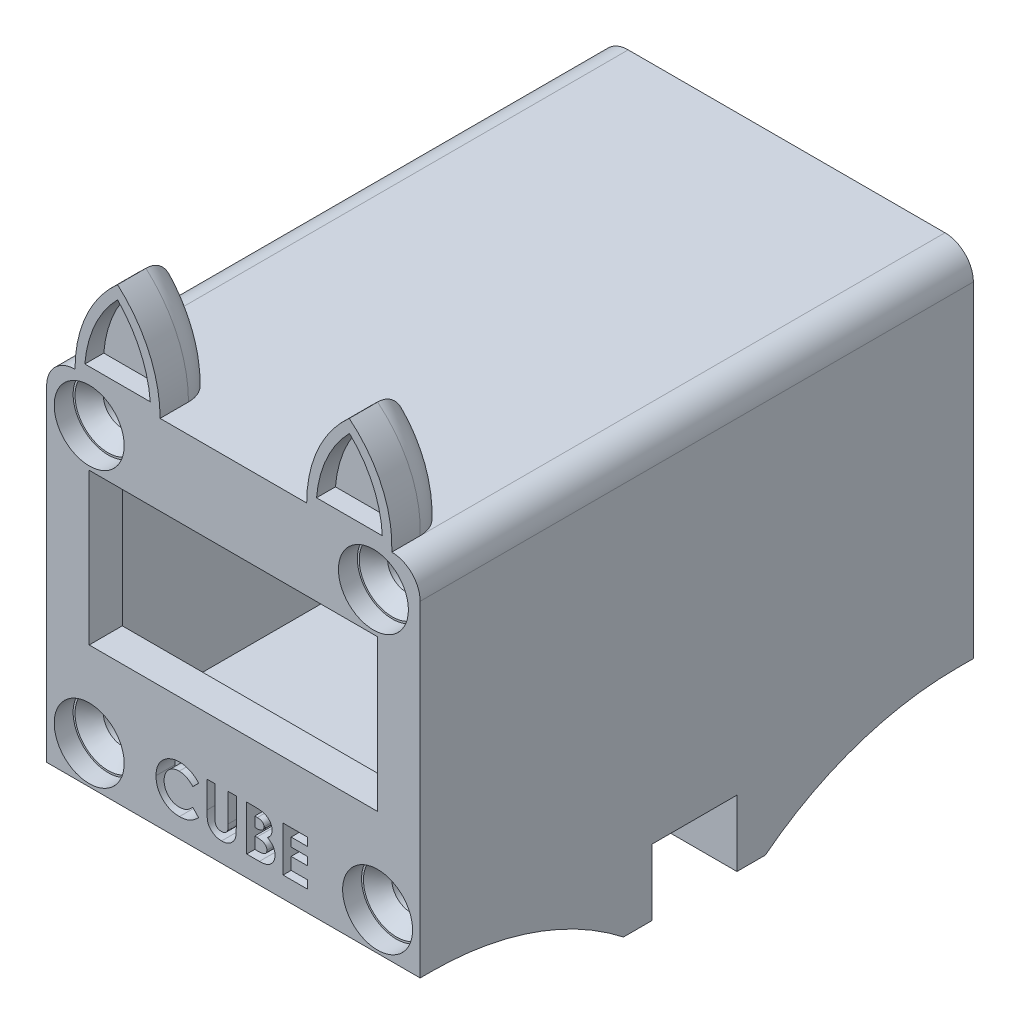
SolidWorks part; units mm, degrees
ref_plane "Plan de face" through (0, 0, 0) normal (0, 0, 1) x (1, 0, 0)
ref_plane "Plan de dessus" through (0, 0, 0) normal (0, 1, 0) x (1, 0, 0)
ref_plane "Plan de droite" through (0, 0, 0) normal (1, 0, 0) x (0, 0, -1)
sketch "Esquisse1" plane through (0, 0, 0) normal (0, 0, 1) x (1, 0, 0)
  line L0 (-17.8827, 11.8632) -> (15.6173, 11.8632)
  line L1 (-20.8827, 8.8632) -> (-20.8827, -25.6368)
  line L2 (18.6173, 8.8632) -> (18.6173, -25.6368)
  line L3 (-20.8827, -25.6368) -> (18.6173, -25.6368)
  line L5 (-16.3827, 3.3632) -> (14.1173, 3.3632)
  line L6 (-16.3827, 3.3632) -> (-16.3827, -12.6368)
  line L7 (-16.3827, -12.6368) -> (14.1173, -12.6368)
  line L8 (14.1173, 3.3632) -> (14.1173, -12.6368)
  arc A0 (18.6173, 8.8632) -> (15.6173, 11.8632) centre (15.6173, 8.8632) ccw
  arc A1 (-20.8827, 8.8632) -> (-17.8827, 11.8632) centre (-17.8827, 8.8632) cw
  point P6 (18.6173, 11.8632)
  point P9 (-20.8827, 11.8632)
  dimension "D3" = 3
  dimension "D1" = 39.5
  dimension "D2" = 37.5
  dimension "D4" = 8.5
  dimension "D5" = 4.5
  dimension "D6" = 16
  dimension "D7" = 4.5
extrude "Boss.-Extru.1" add sketch "Esquisse1" along normal blind 3.5
sketch "Esquisse2" plane through (0, 0, 0) normal (0, 0, -1) x (-1, 0, 0)
  line L8 (-17.1173, 8.8632) -> (-17.1173, -24.1368)
  line L9 (-17.1173, -24.1368) -> (19.3827, -24.1368)
  line L10 (19.3827, -24.1368) -> (19.3827, 8.8632)
  line L11 (17.8827, 10.3632) -> (-15.6173, 10.3632)
  line L12 (-17.1173, 8.8632) -> (-17.1173, -24.1368)
  line L13 (-17.1173, -24.1368) -> (19.3827, -24.1368)
  line L14 (19.3827, -24.1368) -> (19.3827, 8.8632)
  line L15 (17.8827, 10.3632) -> (-15.6173, 10.3632)
  line L20 (-18.6173, 8.8632) -> (-18.6173, -25.6368)
  line L21 (-18.6173, -25.6368) -> (20.8827, -25.6368)
  line L22 (20.8827, -25.6368) -> (20.8827, 8.8632)
  line L23 (17.8827, 11.8632) -> (-15.6173, 11.8632)
  line L24 (-18.6173, 8.8632) -> (-18.6173, -25.6368)
  line L25 (-18.6173, -25.6368) -> (20.8827, -25.6368)
  line L26 (20.8827, -25.6368) -> (20.8827, 8.8632)
  line L27 (17.8827, 11.8632) -> (-15.6173, 11.8632)
  arc A4 (-15.6173, 10.3632) -> (-17.1173, 8.8632) centre (-15.6173, 8.8632) ccw
  arc A5 (19.3827, 8.8632) -> (17.8827, 10.3632) centre (17.8827, 8.8632) ccw
  arc A6 (-15.6173, 10.3632) -> (-17.1173, 8.8632) centre (-15.6173, 8.8632) ccw
  arc A7 (19.3827, 8.8632) -> (17.8827, 10.3632) centre (17.8827, 8.8632) ccw
  arc A10 (-15.6173, 11.8632) -> (-18.6173, 8.8632) centre (-15.6173, 8.8632) ccw
  arc A11 (20.8827, 8.8632) -> (17.8827, 11.8632) centre (17.8827, 8.8632) ccw
  arc A12 (-15.6173, 11.8632) -> (-18.6173, 8.8632) centre (-15.6173, 8.8632) ccw
  arc A13 (20.8827, 8.8632) -> (17.8827, 11.8632) centre (17.8827, 8.8632) ccw
  dimension "D1" = 1.5
  dimension "D2" = 0
extrude "Boss.-Extru.2" add sketch "Esquisse2" along normal blind 55
sketch "Esquisse3" plane through (0, 0, 0) normal (0, 0, -1) x (-1, 0, 0)
  line L0 (-17.1173, -24.1368) -> (19.3827, -24.1368) construction
  line L1 (-17.1173, -24.1368) -> (19.3827, -24.1368)
  line L2 (-17.1173, -24.1368) -> (-17.1173, -19.1368)
  line L3 (-17.1173, -19.1368) -> (19.3827, -19.1368)
  line L4 (19.3827, -24.1368) -> (19.3827, -19.1368)
  line L5 (-17.1173, -24.1368) -> (19.3827, -24.1368) construction
  line L6 (19.3827, -24.1368) -> (19.3827, 8.8632) construction
  line L7 (17.8827, 10.3632) -> (-15.6173, 10.3632) construction
  line L8 (-17.1173, 10.3632) -> (19.3827, 10.3632)
  line L9 (-17.1173, 10.3632) -> (-17.1173, 5.3632)
  line L10 (-17.1173, 5.3632) -> (19.3827, 5.3632)
  line L11 (19.3827, 10.3632) -> (19.3827, 5.3632)
  line L12 (-17.1173, 8.8632) -> (-17.1173, -24.1368) construction
  line L13 (-5.1173, -19.1368) -> (7.3827, -19.1368)
  line L14 (-5.1173, -19.1368) -> (-5.1173, -21.6368)
  line L15 (-5.1173, -21.6368) -> (7.3827, -21.6368)
  line L16 (7.3827, -19.1368) -> (7.3827, -21.6368)
  line L17 (-5.1173, 10.3632) -> (7.3827, 10.3632)
  line L18 (-5.1173, 10.3632) -> (-5.1173, 5.3632)
  line L19 (-5.1173, 5.3632) -> (7.3827, 5.3632)
  line L20 (7.3827, 10.3632) -> (7.3827, 5.3632)
  line M10 (17.8827, 10.3632) -> (-15.6173, 10.3632)
  arc M11 (-15.6173, 10.3632) -> (-17.1173, 8.8632) centre (-15.6173, 8.8632) ccw
  line M12 (-17.1173, 8.8632) -> (-17.1173, -24.1368)
  line M13 (-17.1173, -24.1368) -> (19.3827, -24.1368)
  line M14 (19.3827, -24.1368) -> (19.3827, 8.8632)
  arc M15 (19.3827, 8.8632) -> (17.8827, 10.3632) centre (17.8827, 8.8632) ccw
  dimension "D1" = 5
  dimension "D2" = 0
  dimension "D3" = 5
  dimension "D4" = 2.5
  dimension "D5" = 12
  dimension "D6" = 12
  dimension "D7" = 12
  dimension "D8" = 12
  dimension "D9" = 0
  dimension "D10" = 0
extrude "Boss.-Extru.3" add sketch "Esquisse3" along normal blind 1.5 contours L18 L10 M10 M11 M12 | L20 L10 M10 M14 M15 | L3 L16 L15 L14 M12 M13 M14 region at (-1.1327, -21.8951, 0) region at (11.0713, 7.8456, 0) region at (-13.3367, 7.8456, 0)
fillet "Congé1" radius 2.5 1 edges at (-1.1327, -21.6368, -1.5)
sketch "Esquisse8" plane through (0, 0, 0) normal (0, 0, -1) x (-1, 0, 0)
  line L0 (7.3827, 10.3632) -> (7.3827, 5.3632) construction
  line L1 (-5.1173, 5.3632) -> (7.3827, 5.3632)
  line L2 (-5.1173, 5.3632) -> (-5.1173, 10.3632)
  line L3 (-5.1173, 10.3632) -> (7.3827, 10.3632)
  line L4 (7.3827, 5.3632) -> (7.3827, 10.3632)
  line L5 (7.3827, 10.3632) -> (7.3827, 5.3632) construction
extrude "Enlèv. mat.-Extru.6" cut sketch "Esquisse8" against normal blind 2
sketch "Esquisse4" plane through (0, 0, 3.5) normal (0, 0, 1) x (1, 0, 0)
  line L0 (-20.8827, 7.4632) -> (18.6173, 7.4632) construction
  line L1 (-20.8827, 8.8632) -> (-20.8827, -25.6368) construction
  line L2 (18.6173, -25.6368) -> (18.6173, 8.8632) construction
  line L4 (-20.8827, -25.6368) -> (18.6173, -25.6368) construction
  line L5 (14.1173, -25.6368) -> (14.1173, 11.8632) construction
  line L6 (15.6173, 11.8632) -> (-17.8827, 11.8632) construction
  line L8 (-16.3827, -25.6368) -> (-16.3827, 11.8632) construction
  line L10 (-20.8827, -21.6368) -> (18.6173, -21.6368) construction
  circle A0 centre (-16.3827, 7.4632) radius 2
  circle A1 centre (13.6721, 7.4632) radius 2
  circle A2 centre (14.1173, -21.6368) radius 2
  circle A3 centre (-16.3827, -21.6368) radius 2
  point P6 (-16.3827, 7.4632)
  point P17 (13.6721, 7.4632)
  point P18 (14.1173, -21.6368)
  point P19 (-16.3827, -21.6368)
  dimension "D5" = 4
  dimension "D6" = 4
  dimension "D7" = 4
  dimension "D8" = 4
  dimension "D1" = 4
  dimension "D2" = 4.5
  dimension "D3" = 4.4
  dimension "D4" = 4.5
extrude "Enlèv. mat.-Extru.1" cut sketch "Esquisse4" against normal blind 9.5
sketch "Esquisse5" plane through (0, 0, 3.5) normal (0, 0, 1) x (1, 0, 0)
  line L0 (-15.5568, -23.4583) -> (13.2914, -23.4583) construction
  line L1 (-20.8827, -25.6368) -> (18.6173, -25.6368) construction
  circle A0 centre (-16.3827, -21.6368) radius 3.7
  circle A1 centre (13.6721, 7.4632) radius 3.7
  circle A2 centre (-16.3827, 7.4632) radius 3.7
  circle A3 centre (14.1173, -21.6368) radius 3.7
  circle A4 centre (-16.3827, -21.6368) radius 2 construction
  circle A5 centre (14.1173, -21.6368) radius 2 construction
  text T0 "<b>CUBE</b>" font "Century Gothic" height in points 18
  dimension "D1" = 7.4
  dimension "D2" = 7.4
  dimension "D3" = 7.4
  dimension "D4" = 7.4
  dimension "D5" = 180
extrude "Enlèv. mat.-Extru.5" cut sketch "Esquisse5" against normal blind 2
chamfer "Chanfrein1" distance 1.5 angle 45 4 edges at (-14.3827, -21.6368, 1.5) (-14.3827, 7.4632, 1.5) (15.6721, 7.4632, 1.5) (16.1173, -21.6368, 1.5)
sketch "Esquisse6" plane through (0, 0, -55) normal (0, 0, -1) x (-1, 0, 0)
  line L0 (1.1327, 10.3632) -> (1.1327, -24.1368) construction
  line L1 (7.3827, 10.3632) -> (-5.1173, 10.3632) construction
  line L2 (-17.1173, -24.1368) -> (19.3827, -24.1368) construction
  line L3 (-2.6173, 8.1132) -> (-2.6173, 10.3632)
  line L4 (17.8827, 10.3632) -> (-15.6173, 10.3632) construction
  line L5 (-2.6173, 10.3632) -> (-2.6173, 11.8632)
  line L6 (4.8827, 8.1132) -> (4.8827, 10.3632)
  line L7 (1.1327, -6.8868) -> (9.6914, -6.8868) construction
  line L8 (4.8827, -21.8868) -> (4.8827, -24.1368)
  line L9 (-2.6173, -24.1368) -> (4.8827, -24.1368)
  line L10 (-2.6173, -21.8868) -> (-2.6173, -24.1368)
  line L11 (17.8827, 11.8632) -> (-15.6173, 11.8632) construction
  line L12 (-2.6173, 11.8632) -> (4.8827, 11.8632)
  line L13 (4.8827, 11.8632) -> (4.8827, 10.3632)
  line L14 (4.8827, -24.1368) -> (4.8827, -25.6368)
  line L15 (-18.6173, -25.6368) -> (20.8827, -25.6368) construction
  line L16 (4.8827, -25.6368) -> (-2.6173, -25.6368)
  line L17 (-2.6173, -25.6368) -> (-2.6173, -24.1368)
  circle A0 centre (1.1327, 8.1132) radius 2.25
  circle A1 centre (1.1327, 8.1132) radius 3.75
  circle A2 centre (1.1327, -21.8868) radius 3.75
  circle A3 centre (1.1327, -21.8868) radius 2.25
  point P31 (1.1327, 11.8632)
  line M6 (-18.6173, -25.6368) -> (20.8827, -25.6368)
  line M9 (17.8827, 11.8632) -> (-15.6173, 11.8632)
  line M12 (-15.6173, 10.3632) -> (17.8827, 10.3632)
  line M15 (19.3827, -24.1368) -> (-17.1173, -24.1368)
  dimension "D1" = 4.5
  dimension "D2" = 3.75
extrude "Boss.-Extru.5" add sketch "Esquisse6" against normal blind 7 contours A2 L10 M15 | A2 L17 M6 M15 | A2 L16 L14 M15 | A2 L9 M15 | L8 A2 M15 | A3 L9 A2 M15 | A1 A0 M12 | A1 L12 L5 M12 | A1 L3 M12 | A1 M12 | A1 L13 M12 M9 | A1 L6 M12 region at (2.3337, 9.2686, -55) region at (2.3968, 9.8125, -55) region at (1.6458, 11.2886, -55) region at (-4.6622, 9.8125, -55) region at (-1.1327, 10.9748, -55) region at (-3.9112, 11.2886, -55) region at (-4.5991, -23.0423, -55) region at (-4.6622, -23.5862, -55) region at (-3.9112, -25.0623, -55) region at (2.3968, -23.5862, -55) region at (-1.1327, -24.7485, -55) region at (1.6458, -25.0623, -55)
sketch "Esquisse7" plane through (0, 0, -55) normal (0, 0, -1) x (-1, 0, 0)
  line L0 (7.3827, 10.3632) -> (-5.1173, 10.3632) construction
  line L1 (-3.1173, 10.3632) -> (5.3827, 10.3632)
  line L2 (-3.1173, 10.3632) -> (-3.1173, 8.1132)
  line L3 (-3.1173, 8.1132) -> (5.3827, 8.1132)
  line L4 (5.3827, 10.3632) -> (5.3827, 8.1132)
  line L5 (-2.6173, 8.1132) -> (-2.6173, 10.3632) construction
  line L6 (4.8827, 8.1132) -> (4.8827, 10.3632) construction
  arc A0 (-3.1173, 8.1132) -> (5.3827, 8.1132) centre (1.1327, 8.1132) ccw
  arc A1 (4.8827, 8.1132) -> (-2.6173, 8.1132) centre (1.1327, 8.1132) cw
  line M13 (4.8827, 8.1132) -> (4.8827, 10.3632)
  line M14 (4.8827, 10.3632) -> (17.8827, 10.3632)
  line M24 (-15.6173, 10.3632) -> (-2.6173, 10.3632)
  line M25 (-2.6173, 10.3632) -> (-2.6173, 8.1132)
  arc M26 (-2.6173, 8.1132) -> (4.8827, 8.1132) centre (1.1327, 8.1132) ccw
  dimension "D1" = 2.25
  dimension "D2" = 0.5
  dimension "D3" = 0.5
extrude "Boss.-Extru.6" add sketch "Esquisse7" against normal blind 7 contours L3 A0 M26 | L4 L3 M14 M13 | L2 L3 M25 M24 region at (2.8673, 9.2382, -55) region at (2.8673, 8.0181, -55) region at (-5.1327, 9.2382, -55)
sketch "Esquisse10" plane through (0, 0, 3.5) normal (0, 0, 1) x (1, 0, 0)
  line L0 (-17.8827, 11.8632) -> (15.6173, 11.8632)
  line L1 (15.6173, 11.8632) -> (-17.8827, 11.8632) construction
  line L2 (-13.3827, 11.8632) -> (-13.3827, 21.8632) construction
  line L3 (-13.3827, 21.8632) -> (11.1173, 21.8632) construction
  line L4 (11.1173, 21.8632) -> (11.1173, 11.8632) construction
  line L5 (-13.3827, 11.8632) -> (-8.8827, 11.8632) construction
  line L6 (11.1173, 11.8632) -> (6.6173, 11.8632) construction
  arc A0 (18.6173, 8.8632) -> (15.6173, 11.8632) centre (15.6173, 8.8632) ccw construction
  arc A1 (-17.8827, 11.8632) -> (-13.3827, 21.8632) centre (-4.5216, 11.8632) cw
  arc A2 (-8.8827, 11.8632) -> (-13.3827, 21.8632) centre (-22.2438, 11.8632) ccw
  arc A3 (6.6173, 11.8632) -> (11.1173, 21.8632) centre (19.9784, 11.8632) cw
  arc A4 (11.1173, 21.8632) -> (15.6173, 11.8632) centre (3.4132, 12.3838) cw
  dimension "D1" = 4.5
  dimension "D2" = 4.5
  dimension "D3" = 10
  dimension "D4" = 4.5
  dimension "D5" = 4.5
extrude "Boss.-Extru.7" add sketch "Esquisse10" against normal blind 6 contours A4 A3 L0 | L0 A2 A1 region at (-13.3827, 15.7145, 3.5) region at (11.1634, 15.7373, 3.5)
fillet "Congé2" radius 3 4 edges at (14.5525, 17.3965, -2.5) (7.7941, 17.3461, -2.5) (-10.0595, 17.3461, -2.5) (-16.7059, 17.3461, -2.5)
sketch "Esquisse12" plane through (0, 0, 3.5) normal (0, 0, 1) x (1, 0, 0)
  line L0 (-17.8827, 11.8632) -> (-8.8827, 11.8632)
  line L1 (6.6173, 11.8632) -> (15.6173, 11.8632)
  line L2 (-16.8422, 12.8632) -> (-9.9232, 12.8632)
  line L3 (7.6578, 12.8632) -> (14.6135, 12.8632)
  arc A0 (-17.8827, 11.8632) -> (-13.3827, 21.8632) centre (-4.5216, 11.8632) cw
  arc A1 (-8.8827, 11.8632) -> (-13.3827, 21.8632) centre (-22.2438, 11.8632) ccw
  arc A2 (6.6173, 11.8632) -> (11.1173, 21.8632) centre (19.9784, 11.8632) cw
  arc A3 (11.1173, 21.8632) -> (15.6173, 11.8632) centre (3.2911, 12.3289) cw
  arc A4 (-9.9232, 12.8632) -> (-13.3827, 20.4816) centre (-22.2438, 11.8632) ccw
  arc A5 (-16.8422, 12.8632) -> (-13.3827, 20.4816) centre (-4.5216, 11.8632) cw
  arc A6 (11.1409, 20.5058) -> (14.6135, 12.8632) centre (3.2911, 12.3289) cw
  arc A7 (7.6578, 12.8632) -> (11.1409, 20.5058) centre (19.9784, 11.8632) cw
  dimension "D1" = 1
extrude "Enlèv. mat.-Extru.7" cut sketch "Esquisse12" against normal blind 2 contours L2 A4 A5 | L3 A6 A7
sketch "Esquisse13" plane through (0, -25.6368, 0) normal (0, -1, 0) x (1, 0, 0)
  line L0 (-20.8827, 3.5) -> (-20.8827, -55) construction
  line L1 (-20.8827, -18) -> (18.6173, -18)
  line L2 (-20.8827, -18) -> (-20.8827, -21)
  line L3 (-20.8827, -21) -> (18.6173, -21)
  line L4 (18.6173, -18) -> (18.6173, -21)
  line L5 (18.6173, 3.5) -> (18.6173, -55) construction
  line L6 (18.6173, -55) -> (-20.8827, -55) construction
  line L7 (18.6173, -30) -> (-20.8827, -30)
  line L8 (18.6173, -30) -> (18.6173, -33)
  line L9 (18.6173, -33) -> (-20.8827, -33)
  line L10 (-20.8827, -30) -> (-20.8827, -33)
  dimension "D1" = 3
  dimension "D2" = 3
  dimension "D3" = 9
  dimension "D4" = 22
extrude "Boss.-Extru.8" add sketch "Esquisse13" along normal blind 7
fillet "Congé3" radius 33 2 edges at (-1.1327, -25.6368, -33) (-1.1327, -25.6368, -18)
